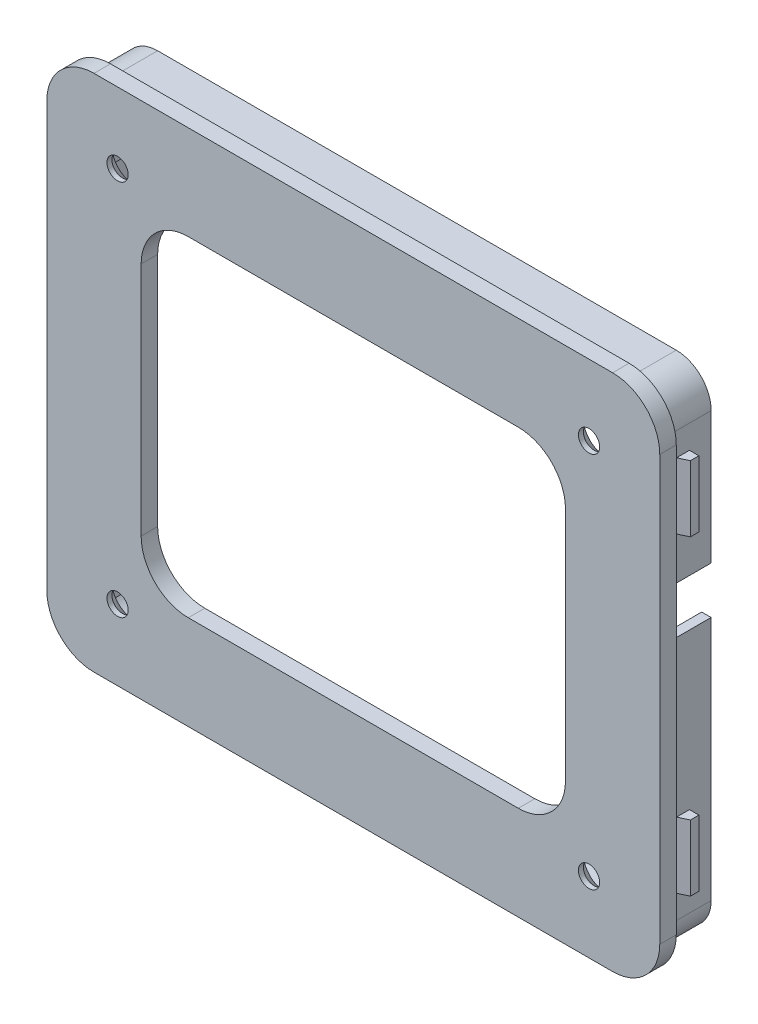
SolidWorks part; units mm, degrees
ref_plane "Přední rovina" through (0, 0, 0) normal (0, 0, 1) x (1, 0, 0)
ref_plane "Horní rovina" through (0, 0, 0) normal (0, 1, 0) x (1, 0, 0)
ref_plane "Pravá rovina" through (0, 0, 0) normal (1, 0, 0) x (0, 0, -1)
sketch "Skica1" plane through (0, 0, 0) normal (0, 0, 1) x (1, 0, 0)
  line L1 (-55, 55) -> (55, 55)
  line L2 (-65, 45) -> (-65, -45)
  line L3 (-55, -55) -> (55, -55)
  line L4 (65, 45) -> (65, -45)
  line L5 (-65, 55) -> (65, -55) construction
  line L6 (-65, -55) -> (65, 55) construction
  arc A0 (55, -55) -> (65, -45) centre (55, -45) ccw
  arc A1 (55, 55) -> (65, 45) centre (55, 45) cw
  arc A2 (-55, 55) -> (-65, 45) centre (-55, 45) ccw
  arc A3 (-65, -45) -> (-55, -55) centre (-55, -45) ccw
  point P0 (0, 0)
  dimension "D3" = 10
  dimension "D1" = 130
  dimension "D2" = 110
extrude "Přidat vysunutím2" add sketch "Skica1" along normal blind 3.5
sketch "Skica3" plane through (0, 0, 0) normal (0, 0, -1) x (-1, 0, 0)
  line L8 (-60.4, 45) -> (-60.4, -45)
  line L9 (-55, -50.4) -> (55, -50.4)
  line L10 (60.4, -45) -> (60.4, 45)
  line L11 (55, 50.4) -> (-55, 50.4)
  line L12 (-62.4, 45) -> (-62.4, -45)
  line L13 (55, 52.4) -> (-55, 52.4)
  line L14 (62.4, -45) -> (62.4, 45)
  line L15 (-55, -52.4) -> (55, -52.4)
  line L16 (-62.4, 45) -> (-62.4, -45)
  line L17 (55, 52.4) -> (-55, 52.4)
  line L18 (62.4, -45) -> (62.4, 45)
  line L19 (-55, -52.4) -> (55, -52.4)
  line L25 (-60.4, 7) -> (-62.4, 7)
  line L26 (-60.4, 7) -> (-60.4, 17)
  line L27 (-60.4, 17) -> (-62.4, 17)
  line L28 (-62.4, 7) -> (-62.4, 17)
  arc A8 (-60.4, -45) -> (-55, -50.4) centre (-55, -45) ccw
  arc A9 (55, -50.4) -> (60.4, -45) centre (55, -45) ccw
  arc A10 (60.4, 45) -> (55, 50.4) centre (55, 45) ccw
  arc A11 (-55, 50.4) -> (-60.4, 45) centre (-55, 45) ccw
  arc A12 (-62.4, -45) -> (-55, -52.4) centre (-55, -45) ccw
  arc A13 (-55, 52.4) -> (-62.4, 45) centre (-55, 45) ccw
  arc A14 (62.4, 45) -> (55, 52.4) centre (55, 45) ccw
  arc A15 (55, -52.4) -> (62.4, -45) centre (55, -45) ccw
  arc A16 (-62.4, -45) -> (-55, -52.4) centre (-55, -45) ccw
  arc A17 (-55, 52.4) -> (-62.4, 45) centre (-55, 45) ccw
  arc A18 (62.4, 45) -> (55, 52.4) centre (55, 45) ccw
  arc A19 (55, -52.4) -> (62.4, -45) centre (55, -45) ccw
  point P32 (0, 0)
  point P33 (0, 0)
  dimension "D3" = 38
  dimension "D6" = 10
  dimension "D1" = 2.6
  dimension "D2" = 2
extrude "Přidat vysunutím3" add sketch "Skica3" along normal blind 10 contours L19 A19 L18 A18 L17 L11 A10 L10 A9 L9 A8 L8 A11 A17 L16 A16 region at (62.0297, 31, 0)
sketch "Skica4" plane through (0, 0, 0) normal (0, 0, -1) x (-1, 0, 0)
  line L1 (-50, -40) -> (50, -40)
  line L2 (-50, -40) -> (-50, 40)
  line L3 (-50, 40) -> (50, 40)
  line L4 (50, -40) -> (50, 40)
  line L5 (-50, -40) -> (50, 40) construction
  line L6 (-50, 40) -> (50, -40) construction
  point P0 (0, 0)
  dimension "D1" = 100
  dimension "D2" = 80
hole_wizard "Válcové zahloubení pro M4 šrouby s plochou hlavou1" positions "3DSkica1" profile "Skica5" countersink size "M4" standard "ANSI Metric" end condition through all
sketch3d "3DSkica1"
  point P0 (-50, -40, 0)
  point P3 (50, -40, 0)
  point P6 (50, 40, 0)
  point P9 (-50, 40, 0)
sketch "Skica5" plane through (-50, -40, 0) normal (1, 0, 0) x (0, 1, 0)
  line L0 (0, 0) -> (0, 3.5)
  line L1 (0, 3.5) -> (2.25, 3.5)
  line L2 (2.25, 3.5) -> (2.25, 2.45)
  line L3 (2.25, 2.45) -> (4.7, 0)
  line L5 (4.7, 0) -> (0, 0)
  line L6 (-2.25, 2.45) -> (-4.7, 0) construction
  line L11 (0, -6.35) -> (0, 107.95) construction
  dimension "Průměr díry skrz" = 4.5
  dimension "Hloubka díry skrz" = 3.5
  dimension "Průměr blíz. kuž. zahloubení" = 9.4
  dimension "Úhel blíz. kuž. zahloubení" = 90
sketch "Skica6" plane through (0, 0, 0) normal (0, 0, -1) x (-1, 0, 0)
  line L1 (-35, -35) -> (35, -35)
  line L2 (-45, -25) -> (-45, 25)
  line L3 (-35, 35) -> (35, 35)
  line L4 (45, -25) -> (45, 25)
  line L5 (-45, -35) -> (45, 35) construction
  line L6 (-45, 35) -> (45, -35) construction
  arc A0 (35, -35) -> (45, -25) centre (35, -25) ccw
  arc A1 (35, 35) -> (45, 25) centre (35, 25) cw
  arc A2 (-45, 25) -> (-35, 35) centre (-35, 25) cw
  arc A3 (-35, -35) -> (-45, -25) centre (-35, -25) cw
  point P0 (0, 0)
  dimension "D3" = 10
  dimension "D1" = 90
  dimension "D2" = 70
extrude "Odebrat vysunutím2" cut sketch "Skica6" against normal through all
sketch "Skica8" plane through (-60.4, 0, 0) normal (1, 0, 0) x (0, 0, -1)
  line L0 (0, 0) -> (10, 0)
  line L1 (0, -45) -> (0, 45) construction
  line L2 (10, -45) -> (10, 45) construction
  line L3 (5, 0) -> (5, 52.9104)
  line L4 (0, -44) -> (0, -36)
  line L5 (8, 44) -> (0, 44)
  line L6 (8, 44) -> (8, 36)
  line L7 (8, 36) -> (0, 36)
  line L8 (0, 44) -> (0, 36)
  line L9 (8, 44) -> (0, 36) construction
  line L10 (8, 36) -> (0, 44) construction
  line L11 (8, -36) -> (0, -36)
  line L12 (8, -44) -> (8, -36)
  line L13 (8, -44) -> (0, -36) construction
  line L14 (8, -36) -> (0, -44) construction
  line L15 (8, -44) -> (0, -44)
  point P8 (4, 40)
  line M8 (0, 45) -> (0, -45)
  dimension "D1" = 15
  dimension "D2" = 4
  dimension "D3" = 8
  dimension "D4" = 8
extrude "Přidat vysunutím4" add sketch "Skica8" along normal blind 5 contours L7 L3 L5 M8 | L7 L6 L5 L3 | L15 L12 L11 M8 region at (-60.4, -40, -4) region at (-60.4, 40, -2.5) region at (-60.4, 40, -6.5)
sketch "Skica9" plane through (-55.4, 0, 0) normal (1, 0, 0) x (0, 0, -1)
  point P12 (4, 40)
hole_wizard "Válcové zahloubení pro M3 šrouby s válcovou hlavou zaoblenou1" positions "3DSkica4" profile "Skica14" counterbore size "M3" standard "ANSI Metric" end condition through all
sketch3d "3DSkica4"
  point P0 (-55.4, 40, -4)
sketch "Skica14" plane through (-55.4, 40, -4) normal (0, 1, 0) x (0, 0, -1)
  line L0 (0, 0) -> (0, 9.6)
  line L1 (0, 9.6) -> (1.7, 9.6)
  line L3 (1.7, 9.6) -> (1.7, 4)
  line L4 (1.7, 4) -> (1.95, 4)
  line L5 (1.95, 4) -> (1.95, 0)
  line L7 (1.95, 0) -> (0, 0)
  line L11 (0, -6.35) -> (0, 107.95) construction
  dimension "Průměr díry skrz" = 3.4
  dimension "Hloubka díry skrz" = 9.6
  dimension "Průměr válcového zahloubení" = 3.9
  dimension "Hloubka válcového zahloubení" = 4
ref_plane "Rovina2" through (0, 0, 0) normal (0, 1, 0) x (1, 0, 0)
mirror "Zrcadlit1" about plane through (0, 0, 0) normal (0, 1, 0) of "Válcové zahloubení pro M3 šrouby s válcovou hlavou zaoblenou1"
sketch "Skica15" plane through (62.4, 0, 0) normal (1, 0, 0) x (0, 0, -1)
  line L0 (0, 0) -> (10, 0)
  line L1 (5.4, -40) -> (2.6, -40)
  line L2 (5.4, -40) -> (5.4, -26)
  line L3 (5.4, -26) -> (2.6, -26)
  line L4 (2.6, -40) -> (2.6, -26)
  line L5 (5.4, -40) -> (2.6, -26) construction
  line L6 (5.4, -26) -> (2.6, -40) construction
  line L7 (10, 7) -> (10, -45) construction
  line L8 (5.4, 26) -> (2.6, 40) construction
  line L9 (2.6, 40) -> (2.6, 26)
  line L10 (5.4, 26) -> (2.6, 26)
  line L11 (5.4, 40) -> (5.4, 26)
  line L12 (5.4, 40) -> (2.6, 40)
  line L13 (5.4, 40) -> (2.6, 26) construction
  point P0 (4, -33)
  point P16 (4, 33)
  dimension "D1" = 15
  dimension "D2" = 14
  dimension "D3" = 2.8
  dimension "D4" = 4
extrude "Přidat vysunutím5" add sketch "Skica15" along normal blind 2 contours L11 L12 L9 L10 | L4 L3 L2 L1 region at (62.4, 33, -4)
chamfer "Zkosení1" distance 1 angle 65 1 edges at (64.4, -33, -2.6) first distance on face at (64.4, -33, -4)
chamfer "Zkosení2" distance 1 angle 65 1 edges at (64.4, 33, -2.6) first distance on face at (64.4, 33, -4)
